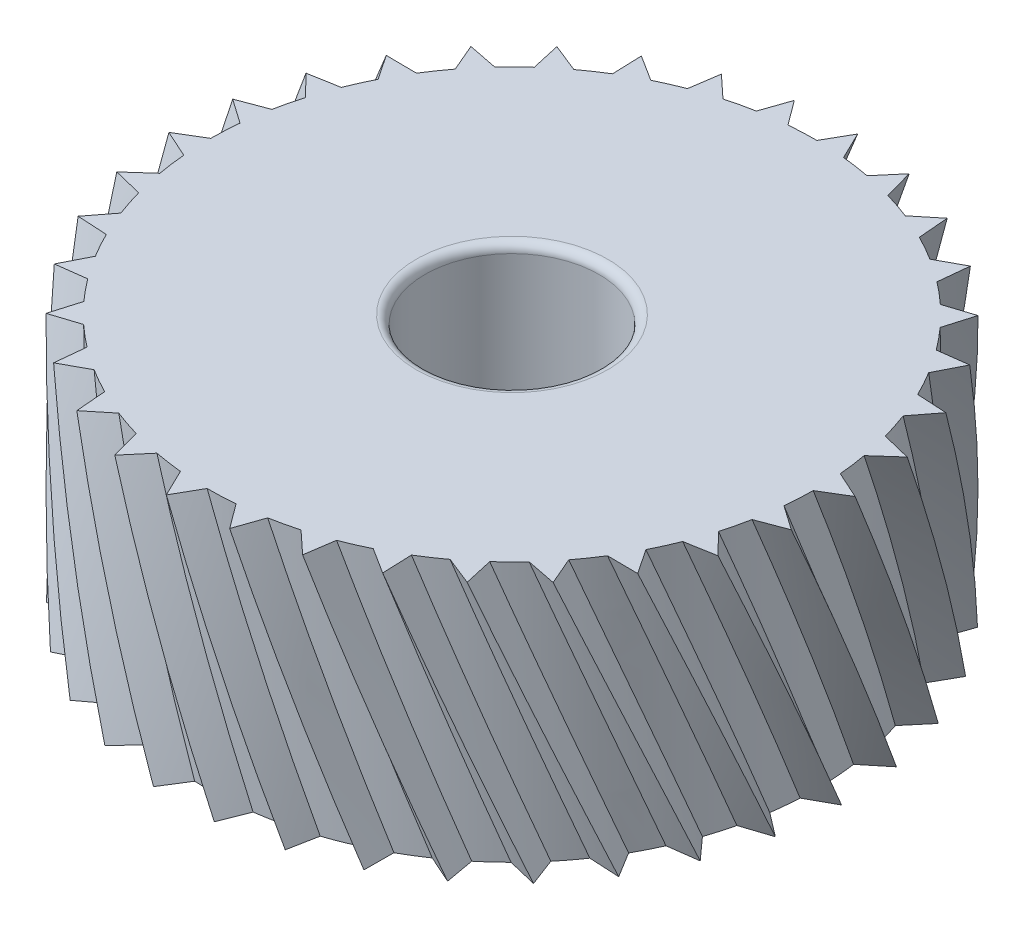
SolidWorks part; units mm, degrees
ref_plane "Plan de face" through (0, 0, 0) normal (0, 0, 1) x (1, 0, 0)
ref_plane "Plan de dessus" through (0, 0, 0) normal (0, 1, 0) x (1, 0, 0)
ref_plane "Plan de droite" through (0, 0, 0) normal (1, 0, 0) x (0, 0, -1)
sketch "Esquisse1" plane through (0, 0, 0) normal (0, 1, 0) x (1, 0, 0)
  circle A0 centre (0, 0) radius 18.75
extrude "Boss.-Extru.2" add sketch "Esquisse1" along normal blind 14.8 contours A0
sketch "Esquisse9" plane through (0, 14.8, 0) normal (0, 1, 0) x (1, 0, 0)
  circle A0 centre (0, 0) radius 4.95
extrude "Enlèv. mat.-Extru.1" cut sketch "Esquisse9" against normal blind 50
sketch "Esquisse11" plane through (0, 0, 0) normal (0, -1, 0) x (-1, 0, 0)
  line L0 (0, 0) -> (18.434, 3.4277) construction
  line L1 (0, 0) -> (18.75, 0) construction
  circle A0 centre (0, 0) radius 17.25
  circle A1 centre (0, 0) radius 18.75 construction
curve "Hélice/Spirale1" pitch 284 height 14.8 turns 0.0521
sketch "Esquisse12" plane through (0, 0, 0) normal (0, -1, 0) x (-1, 0, 0)
  line L0 (0, 0) -> (18.75, 0) construction
  line L1 (0, 0) -> (18.4307, 3.4453) construction
  line L8 (18.4307, 3.4453) -> (20.5689, 1.9124)
  line L9 (20.5689, 1.9124) -> (18.75, 0)
  line L12 (17.2298, 0.8352) -> (18.75, 0)
  line L13 (17.0805, 2.4125) -> (18.4307, 3.4453)
  circle A2 centre (0, 0) radius 17.25 construction
  arc A3 (17.0805, 2.4125) -> (17.2298, 0.8352) centre (0, 0) cw
  circle A7 centre (0, 0) radius 18.75 construction
sweep "Enlèvement de matière-Balayage4" cut profiles "Esquisse12" path "Hélice/Spirale1" align with end faces yes
pattern_circular "Répétition circulaire2" count 34 over 360 about axis through (0, 14.8, 0) along (0, -1, 0) of "Enlèvement de matière-Balayage4" reverse direction yes
fillet "Congé1" radius 0.5 2 edges at (0, 0, 4.95) (0, 14.8, 4.95)
